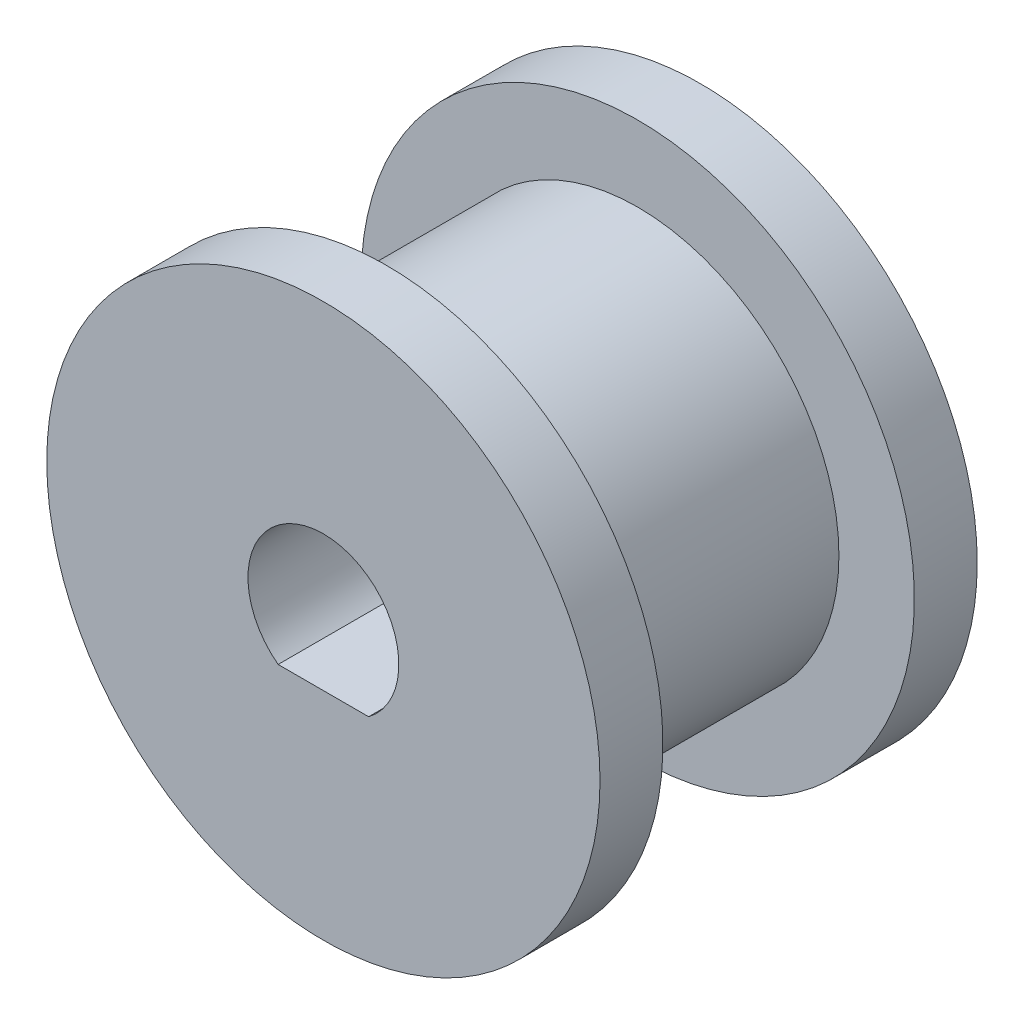
SolidWorks part; units mm, degrees
material "Nylon 101"
ref_plane "Front" through (0, 0, 0) normal (0, 0, 1) x (1, 0, 0)
ref_plane "Top" through (0, 0, 0) normal (0, 1, 0) x (1, 0, 0)
ref_plane "Right" through (0, 0, 0) normal (1, 0, 0) x (0, 0, -1)
sketch "Sketch1" plane through (0, 0, 0) normal (0, 0, 1) x (1, 0, 0)
  line L0 (-1.8, -2.4) -> (1.8, -2.4)
  arc A0 (1.8, -2.4) -> (-1.8, -2.4) centre (0, 0) ccw
  circle A1 centre (0, 0) radius 11
  dimension "D1" = 6
  dimension "D3" = 22
  dimension "D2" = 3.6
extrude "Boss-Extrude1" add sketch "Sketch1" along normal blind 15 contours A1 A0 L0 region at (-10.6889, 0, 0)
sketch "Sketch2" plane through (0, 0, 0) normal (0, 1, 0) x (1, 0, 0)
  line L0 (-11, -2.5) -> (-11, -12.5)
  line L1 (-11, 0) -> (-11, -15) construction
  line L2 (-11, -12.5) -> (-8, -12.5)
  line L3 (-8, -12.5) -> (-8, -2.5)
  line L4 (-8, -2.5) -> (-11, -2.5)
  line L5 (0, 0) -> (0, -15) construction
  line L6 (11, 0) -> (-11, 0) construction
  line L7 (-11, -15) -> (11, -15) construction
  line L8 (0, -7.5) -> (-0.788, -7.5) construction
  dimension "D1" = 10
  dimension "D2" = 3
revolve "Cut-Revolve1" cut sketch "Sketch2" angle 360 about L5
